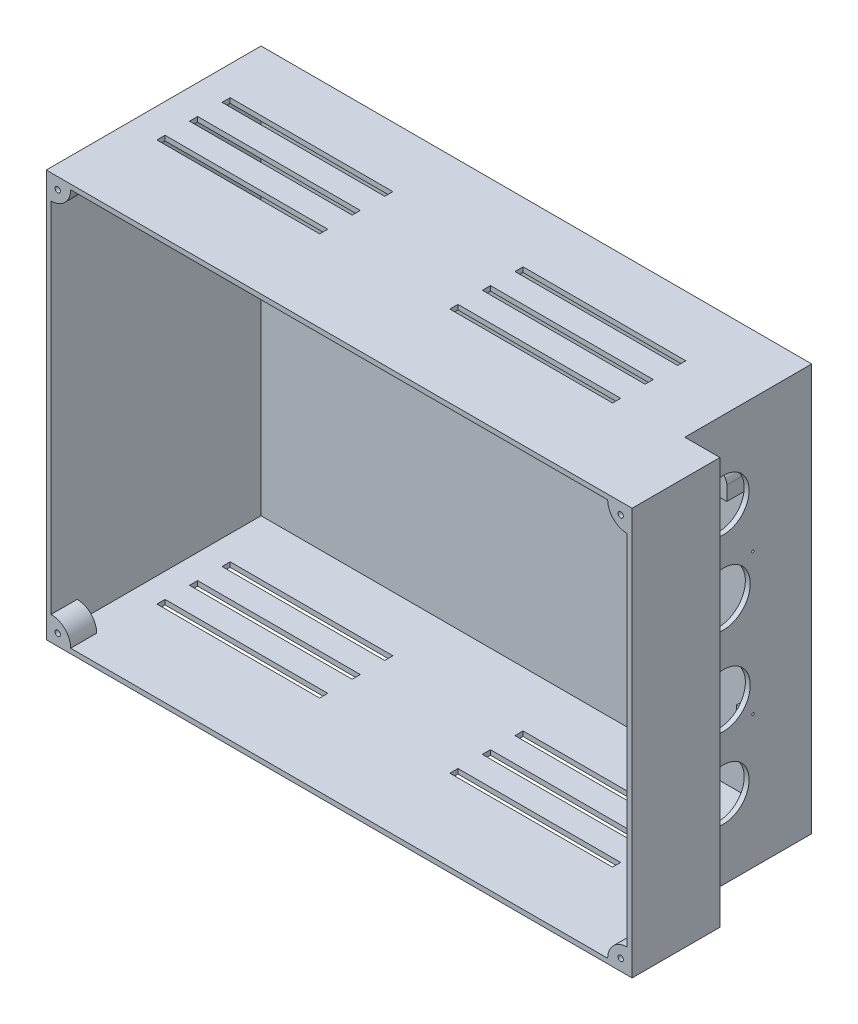
SolidWorks part; units mm, degrees
ref_plane "前视基准面" through (0, 0, 0) normal (0, 0, 1) x (1, 0, 0)
ref_plane "上视基准面" through (0, 0, 0) normal (0, 1, 0) x (1, 0, 0)
ref_plane "右视基准面" through (0, 0, 0) normal (1, 0, 0) x (0, 0, -1)
sketch "草图2" plane through (0, 0, 0) normal (0, 0, 1) x (1, 0, 0)
  line L1 (-90, 62.5) -> (90, 62.5)
  line L2 (-90, 62.5) -> (-90, -62.5)
  line L3 (-90, -62.5) -> (90, -62.5)
  line L4 (90, 62.5) -> (90, -62.5)
  line L5 (-90, 62.5) -> (90, -62.5) construction
  line L6 (-90, -62.5) -> (90, 62.5) construction
  point P0 (0, 0)
  dimension "D1" = 180
  dimension "D2" = 125
extrude "凸台-拉伸1" add sketch "草图2" along normal blind 66
sketch "草图4" plane through (90, 0, 0) normal (1, 0, 0) x (0, 0, -1)
  line L0 (-39, -62.5) -> (-39, 62.5)
  line L1 (-66, 61.5) -> (-66, -61.5) construction
  line L2 (-66, 62.5) -> (0, 62.5) construction
  line L4 (0, -62.5) -> (0, 62.5)
  line L6 (-66, 62.5) -> (-66, -62.5)
  line L9 (0, 62.5) -> (-39, 62.5)
  line L11 (-39, -62.5) -> (0, -62.5)
  line L14 (0, -62.5) -> (0, 62.5)
  line L15 (0, 62.5) -> (-66, 62.5)
  line L16 (-66, -62.5) -> (0, -62.5)
  dimension "D2" = 27
  dimension "D1" = 0
extrude "切除-拉伸2" cut sketch "草图4" against normal offset from surface (10.8 mm away) 2
shell "抽壳1" thickness 1.5 removed face at (0, 0, 66)
sketch "草图6" plane through (79.2, 0, 0) normal (1, 0, 0) x (0, 0, -1)
  line L1 (-16.0647, -23.6651) -> (-20.0647, -23.6651)
  line L2 (-16.0647, -23.6651) -> (-16.0647, -19.6651)
  line L3 (-16.0647, -19.6651) -> (-20.0647, -19.6651)
  line L4 (-20.0647, -23.6651) -> (-20.0647, -19.6651)
  line L5 (-34.2212, -23.6651) -> (-38.2212, -23.6651)
  line L6 (-34.2212, -23.6651) -> (-34.2212, -19.6651)
  line L7 (-34.2212, -19.6651) -> (-38.2212, -19.6651)
  line L8 (-38.2212, -23.6651) -> (-38.2212, -19.6651)
  line L9 (-34.2212, 19.6651) -> (-38.2212, 19.6651)
  line L10 (-34.2212, 19.6651) -> (-34.2212, 23.6651)
  line L11 (-34.2212, 23.6651) -> (-38.2212, 23.6651)
  line L12 (-38.2212, 19.6651) -> (-38.2212, 23.6651)
  line L13 (-16.0647, 19.6651) -> (-20.0647, 19.6651)
  line L14 (-16.0647, 19.6651) -> (-16.0647, 23.6651)
  line L15 (-16.0647, 23.6651) -> (-20.0647, 23.6651)
  line L16 (-20.0647, 19.6651) -> (-20.0647, 23.6651)
  arc A0 (-18.5647, 21.6651) -> (-17.5647, 21.6651) centre (-18.0647, 21.6651) ccw construction
  arc A1 (-17.5647, 21.6651) -> (-18.5647, 21.6651) centre (-18.0647, 21.6651) ccw construction
  arc A2 (-35.7212, 21.6651) -> (-36.7212, 21.6651) centre (-36.2212, 21.6651) ccw construction
  arc A3 (-36.7212, 21.6651) -> (-35.7212, 21.6651) centre (-36.2212, 21.6651) ccw construction
  arc A4 (-36.7212, -21.6651) -> (-35.7212, -21.6651) centre (-36.2212, -21.6651) ccw construction
  arc A5 (-18.5647, -21.6651) -> (-17.5647, -21.6651) centre (-18.0647, -21.6651) ccw construction
  dimension "D10" = 2
  dimension "D1" = 2
  dimension "D2" = 2
  dimension "D3" = 2
  dimension "D4" = 2
  dimension "D5" = 4
  dimension "D6" = 2
  dimension "D7" = 4
  dimension "D8" = 2
  dimension "D9" = 2
  dimension "D11" = 4
  dimension "D12" = 4
  dimension "D13" = 2
  dimension "D14" = 2
  dimension "D15" = 4
  dimension "D16" = 4
extrude "凸台-拉伸2" add sketch "草图6" against normal up to surface (3 mm away)
sketch "草图7" plane through (79.2, 0, 0) normal (1, 0, 0) x (0, 0, -1)
  circle A0 centre (-27.143, -13.5) radius 8.25
  circle A1 centre (-27.143, 13.5) radius 8.25
  circle A2 centre (-18.0647, -21.6651) radius 0.375
  circle A3 centre (-18.0647, 21.6651) radius 0.375
  circle A4 centre (-36.2212, 21.6651) radius 0.375
  circle A5 centre (-36.2212, -21.6651) radius 0.375
  arc A6 (-19.143, -13.5) -> (-35.143, -13.5) centre (-27.143, -13.5) ccw construction
  circle A7 centre (-27.143, 38.5) radius 7.9
  circle A8 centre (-27.143, 38.5) radius 7.65 construction
  circle A9 centre (-27.143, -38.5) radius 7.9
  dimension "D1" = 0.75
  dimension "D2" = 0.25
  dimension "D3" = 0.25
extrude "切除-拉伸3" cut sketch "草图7" against normal up to next
sketch "草图8" plane through (0, -62.5, 0) normal (0, -1, 0) x (1, 0, 0)
  line L0 (-90, 66) -> (90, 66) construction
  line L1 (-81, 41) -> (-31, 41)
  line L2 (-81, 41) -> (-81, 38.5)
  line L3 (-81, 38.5) -> (-31, 38.5)
  line L4 (-31, 41) -> (-31, 38.5)
  line L5 (-90, 66) -> (-90, 0) construction
  line L6 (9, 41) -> (59, 41)
  line L7 (9, 41) -> (9, 38.5)
  line L8 (9, 38.5) -> (59, 38.5)
  line L9 (59, 41) -> (59, 38.5)
  line L10 (9, 31) -> (59, 31)
  line L11 (9, 31) -> (9, 28.5)
  line L12 (9, 28.5) -> (59, 28.5)
  line L13 (59, 31) -> (59, 28.5)
  line L14 (9, 21) -> (59, 21)
  line L15 (9, 21) -> (9, 18.5)
  line L16 (9, 18.5) -> (59, 18.5)
  line L17 (59, 21) -> (59, 18.5)
  line L18 (-81, 31) -> (-31, 31)
  line L19 (-81, 31) -> (-81, 28.5)
  line L20 (-81, 28.5) -> (-31, 28.5)
  line L21 (-31, 31) -> (-31, 28.5)
  line L22 (-81, 21) -> (-31, 21)
  line L23 (-81, 21) -> (-81, 18.5)
  line L24 (-81, 18.5) -> (-31, 18.5)
  line L25 (-31, 21) -> (-31, 18.5)
  dimension "D1" = 2.5
  dimension "D2" = 25
  dimension "D3" = 9
  dimension "D4" = 50
  dimension "D5" = 2
  dimension "D6" = 3
extrude "切除-拉伸4" cut sketch "草图8" against normal up to surface (125 mm away) and the other way through all up to face at (26.4, 62.5, 35)
sketch "草图9" plane through (0, 0, 66) normal (0, 0, 1) x (1, 0, 0)
  line L1 (-88.5, 61) -> (-82.5, 61)
  line L2 (-88.5, 61) -> (-88.5, 55)
  line L5 (0, 0) -> (0, 36.715) construction
  line L6 (0, 0) -> (38.7304, 0) construction
  line L7 (-88.5, -61) -> (-88.5, -55)
  line L8 (-88.5, -61) -> (-82.5, -61)
  line L9 (88.5, -61) -> (82.5, -61)
  line L10 (88.5, -61) -> (88.5, -55)
  line L11 (88.5, 61) -> (88.5, 55)
  line L12 (88.5, 61) -> (82.5, 61)
  circle A0 centre (-86.5, 59) radius 0.825
  arc A1 (-82.5, 61) -> (-88.5, 55) centre (-88.5, 61) cw
  arc A2 (-82.5, -61) -> (-88.5, -55) centre (-88.5, -61) ccw
  circle A3 centre (-86.5, -59) radius 0.825
  circle A4 centre (86.5, -59) radius 0.825
  arc A5 (82.5, -61) -> (88.5, -55) centre (88.5, -61) cw
  arc A6 (82.5, 61) -> (88.5, 55) centre (88.5, 61) ccw
  circle A7 centre (86.5, 59) radius 0.825
  dimension "D1" = 1.65
  dimension "D2" = 2
  dimension "D3" = 2
  dimension "D4" = 6
extrude "凸台-拉伸3" add sketch "草图9" against normal blind 8
sketch "草图10" plane through (0, 0, 1.5) normal (0, 0, 1) x (1, 0, 0)
  line L0 (77.7, -61) -> (77.7, 61) construction
  line L1 (77.7, 50.5757) -> (70.499, 50.5757)
  line L2 (77.7, 50.5757) -> (77.7, 61)
  line L3 (77.7, 61) -> (70.499, 61)
  line L4 (70.499, 50.5757) -> (70.499, 61)
  line L5 (82.5, 61) -> (-82.5, 61) construction
  line L7 (62.513, 50.5757) -> (55.312, 50.5757)
  line L8 (62.513, 50.5757) -> (62.513, 61)
  line L9 (62.513, 61) -> (55.312, 61)
  line L10 (55.312, 50.5757) -> (55.312, 61)
  line L11 (62.513, 22.2546) -> (55.312, 22.2546)
  line L12 (62.513, 22.2546) -> (62.513, 29.6276)
  line L13 (62.513, 29.6276) -> (55.312, 29.6276)
  line L14 (55.312, 22.2546) -> (55.312, 29.6276)
  line L15 (77.7, 61) -> (-88.5, 61) construction
  line L16 (77.7, 22.2546) -> (70.499, 22.2546)
  line L17 (77.7, 22.2546) -> (77.7, 29.6276)
  line L18 (77.7, 29.6276) -> (70.499, 29.6276)
  line L19 (70.499, 22.2546) -> (70.499, 29.6276)
  arc A0 (73.999, 27.2546) -> (73.999, 25.2546) centre (73.999, 26.2546) ccw construction
  arc A1 (59.013, 25.1276) -> (59.013, 27.1276) centre (59.013, 26.1276) ccw construction
  arc A2 (59.013, 27.1276) -> (59.013, 25.1276) centre (59.013, 26.1276) ccw construction
  arc A4 (74.126, 53.5757) -> (74.126, 55.5757) centre (74.126, 54.5757) ccw construction
  circle A5 centre (74.126, 54.5757) radius 0.825
  circle A6 centre (59.14, 54.5757) radius 0.825
  circle A7 centre (59.013, 26.1276) radius 0.825
  circle A8 centre (73.999, 26.2546) radius 0.825
  dimension "D7" = 1.65
  dimension "D6" = 1.65
  dimension "D8" = 1.65
  dimension "D9" = 1.65
  dimension "D1" = 4
  dimension "D2" = 3.5
  dimension "D3" = 3.5
  dimension "D4" = 3.5
  dimension "D5" = 4
extrude "开关螺孔凸台-拉伸4" add sketch "草图10" along normal up to surface (7.8999 mm away)
sketch "草图11" plane through (0, 0, 0) normal (0, 0, -1) x (-1, 0, 0)
  circle A0 centre (-66.76, 36.1607) radius 6.1
  circle A5 centre (-65.482, 49.2417) radius 2.6
  dimension "D1" = 12.2
  dimension "D2" = 5.2
extrude "切除-拉伸5" cut sketch "草图11" against normal up to next
fillet "圆角1" radius 3 4 edges at (62.513, 29.6276, 5.45) (62.513, 50.5757, 5.45) (70.499, 29.6276, 5.45) (70.499, 50.5757, 5.45)
